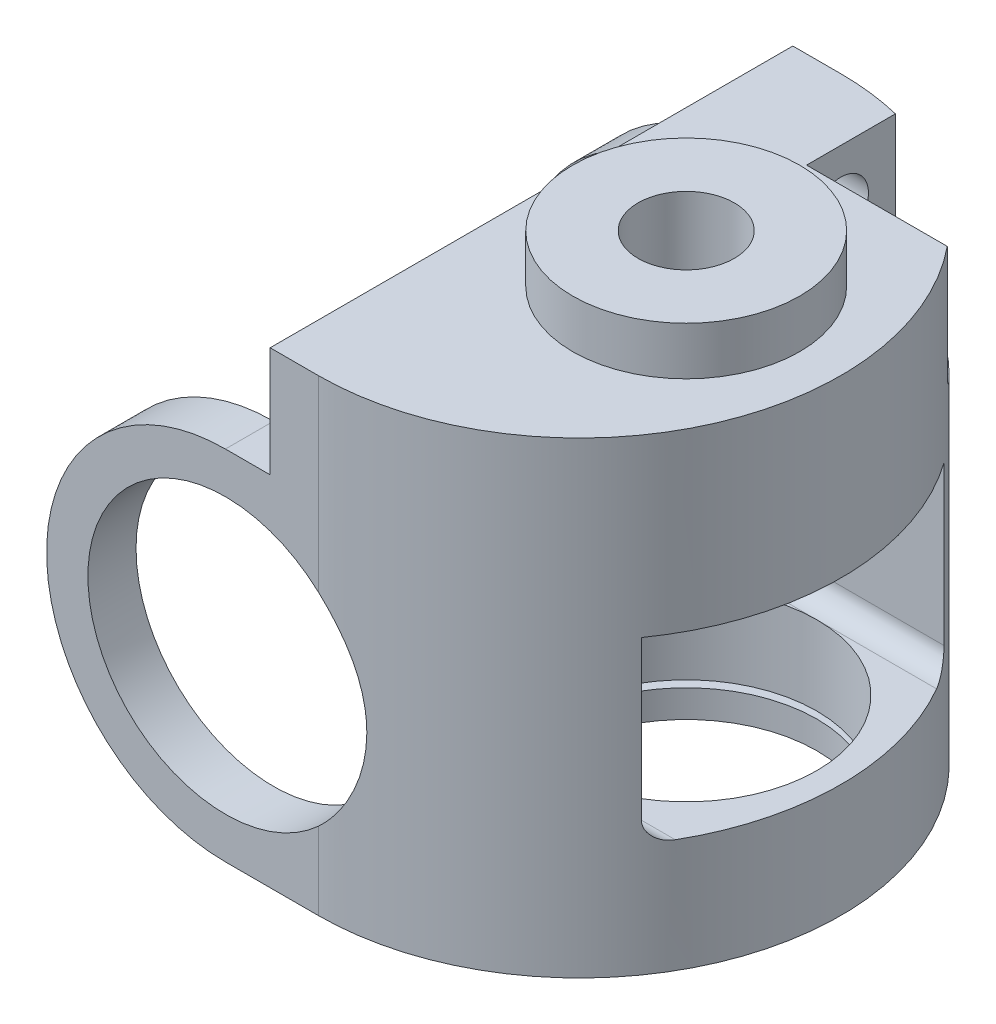
SolidWorks part; units mm, degrees
ref_plane "Plan de face" through (0, 0, 0) normal (0, 0, 1) x (1, 0, 0)
ref_plane "Plan de dessus" through (0, 0, 0) normal (0, 1, 0) x (1, 0, 0)
ref_plane "Plan de droite" through (0, 0, 0) normal (1, 0, 0) x (0, 0, -1)
sketch "Sketch2" plane through (0, 0, 0) normal (0, 1, 0) x (1, 0, 0)
  line L0 (-3.5, -19) -> (-3.5, 19)
  line L1 (-3.5, 19) -> (0, 19)
  line L2 (-3.5, -19) -> (0, -19)
  line L3 (19, 0) -> (19, 16.5672) construction
  arc A0 (0, -19) -> (0, 19) centre (0, 0) ccw
  circle A1 centre (7.75, 0) radius 3.5
  point P7 (-3.5, 0)
  dimension "D1" = 19
  dimension "D3" = 22.5
  dimension "D4" = 11.25
  dimension "D5" = 7
  dimension "D2" = 38
extrude "Boss-Extrude1" add sketch "Sketch2" along normal blind 34
sketch "Sketch19" plane through (0, 34, 0) normal (0, 1, 0) x (1, 0, 0)
  circle A0 centre (7.75, 0) radius 8.25
  circle A1 centre (7.75, 0) radius 3.5
  dimension "D1" = 16.5
  dimension "D2" = 7
extrude "Boss-Extrude3" add sketch "Sketch19" along normal blind 3.5
sketch "Sketch3" plane through (0, 0, 19) normal (0, 0, 1) x (1, 0, 0)
  line L3 (-3.5, 0) -> (-6.75, 0)
  line L4 (-6.75, 26) -> (-3.5, 26)
  line L5 (-3.5, 34) -> (-3.5, 0) construction
  arc A0 (-6.75, 26) -> (-6.75, 0) centre (-6.75, 13) ccw
  line M4 (-3.5, 34) -> (-3.5, 0)
  dimension "D1" = 26
  dimension "D2" = 3.25
extrude "Boss-Extrude2" add sketch "Sketch3" against normal blind 3.5 contours A0 M4 region at (-10.5428, 13, 19)
sketch "Sketch4" plane through (0, 0, 19) normal (0, 0, 1) x (1, 0, 0)
  circle A0 centre (-6.75, 13) radius 10
  dimension "D1" = 20
extrude "Cut-Extrude1" cut sketch "Sketch4" against normal up to surface (3.5 mm away) up to face at (-8.375, 13, 15.5)
pattern_linear "LPattern4" count 2 spacing 34.5 along (0, 0, -1) of "Boss-Extrude2", "Cut-Extrude1"
sketch "Sketch6" plane through (-3.5, 0, 0) normal (1, 0, 0) x (0, 0, -1)
  line L0 (15.5, 0) -> (-15.5, 0) construction
  line L1 (11, 21.25) -> (-11, 21.25)
  line L2 (11, 21.25) -> (11, 9.75)
  line L3 (9.5, 8.25) -> (-9.5, 8.25)
  line L4 (-11, 21.25) -> (-11, 9.75)
  arc A0 (-11, 9.75) -> (-9.5, 8.25) centre (-9.5, 9.75) ccw
  arc A1 (11, 9.75) -> (9.5, 8.25) centre (9.5, 9.75) cw
  point P6 (0, 8.25)
  point P10 (-11, 8.25)
  point P13 (11, 8.25)
  dimension "D4" = 1.5
  dimension "D1" = 8.25
  dimension "D2" = 22
  dimension "D3" = 13
extrude "Cut-Extrude3" cut sketch "Sketch6" along normal through all
sketch "Sketch7" plane through (0, 0, 15.5) normal (0, 0, -1) x (-1, 0, 0)
  circle A3 centre (6.75, 13) radius 13.5
  dimension "D3" = 27
extrude "Cut-Extrude4" cut sketch "Sketch7" along normal blind 4.5 contours A3
pattern_linear "LPattern3" count 2 spacing 26.5 along (0, 0, -1) of "Cut-Extrude4"
sketch "Sketch16" plane through (-3.5, 0, 0) normal (-1, 0, 0) x (0, 0, 1)
  line L0 (19, 34) -> (19, 26) construction
  line L1 (-19, 34) -> (19, 34) construction
  point P0 (11, 31.5)
  dimension "D1" = 8
  dimension "D2" = 2.5
hole_wizard "M2 Tapped Hole1" positions "Sketch16" profile "Sketch15" tap size "M2" standard "ISO"
sketch "Sketch15" plane through (-3.5, 31.5, 11) normal (0, 1, 0) x (0, 0, 1)
  line L0 (0, 0) -> (0, 5.9807)
  line L1 (0, 5.9807) -> (0.8, 5.5)
  line L2 (0.8, 5.5) -> (0.8, 0)
  line L5 (0.8, 0) -> (0, 0)
  line L10 (0, 5.9807) -> (-0.8, 5.5) construction
  line L11 (0, -6.35) -> (0, 107.95) construction
  dimension "Tap Drill Dia." = 1.6
  dimension "Tap Drill Depth" = 5.5
  dimension "Drill Angle" = 118
cosmetic thread "Hole Thread1" parameters "D1"=4.5, "D2"=2
sketch "Sketch17" plane through (-3.5, 0, 0) normal (-1, 0, 0) x (0, 0, 1)
  line L0 (-19, 34) -> (-19, 26) construction
  line L1 (-19, 34) -> (19, 34) construction
  circle A1 centre (-14.5, 30) radius 2
  dimension "D1" = 4
  dimension "D2" = 4.5
  dimension "D3" = 4
extrude "Cut-Extrude5" cut sketch "Sketch17" against normal blind 8
sketch "Sketch18" plane through (4.5, 0, 0) normal (-1, 0, 0) x (0, 0, 1)
  line L0 (-19, 34) -> (-19, 26) construction
  line L1 (-19, 24.5) -> (-13.5, 24.5)
  line L2 (-19, 24.5) -> (-19, 34)
  line L3 (-19, 34) -> (-12, 34)
  line L4 (-12, 26) -> (-12, 34)
  line L5 (-19, 34) -> (19, 34) construction
  arc A2 (-12, 26) -> (-13.5, 24.5) centre (-13.5, 26) cw
  dimension "D1" = 9.5
  dimension "D2" = 7
  dimension "D3" = 1.5
extrude "Cut-Extrude6" cut sketch "Sketch18" against normal up to next
sketch "Sketch20" plane through (0, 21.25, 0) normal (0, -1, 0) x (1, 0, 0)
  circle A0 centre (7.75, 0) radius 9.75
  dimension "D1" = 19.5
extrude "Cut-Extrude7" cut sketch "Sketch20" against normal blind 6.25
sketch "Sketch21" plane through (0, 27.5, 0) normal (0, -1, 0) x (1, 0, 0)
  circle A0 centre (7.75, 0) radius 8.5
  dimension "D1" = 17
extrude "Cut-Extrude8" cut sketch "Sketch21" against normal blind 0.5
sketch "Sketch22" plane through (0, 8.25, 0) normal (0, 1, 0) x (1, 0, 0)
  circle A0 centre (7.75, 0) radius 9.5
  dimension "D1" = 19
extrude "Cut-Extrude9" cut sketch "Sketch22" against normal blind 5.75
sketch "Sketch23" plane through (0, 2.5, 0) normal (0, 1, 0) x (1, 0, 0)
  circle A0 centre (7.75, 0) radius 10.5
  dimension "D1" = 21
extrude "Cut-Extrude10" cut sketch "Sketch23" against normal blind 0.5
sketch "Sketch24" plane through (0, 2, 0) normal (0, 1, 0) x (1, 0, 0)
  circle A0 centre (7.75, 0) radius 9.5
  dimension "D1" = 19
extrude "Cut-Extrude11" cut sketch "Sketch24" against normal blind 2
